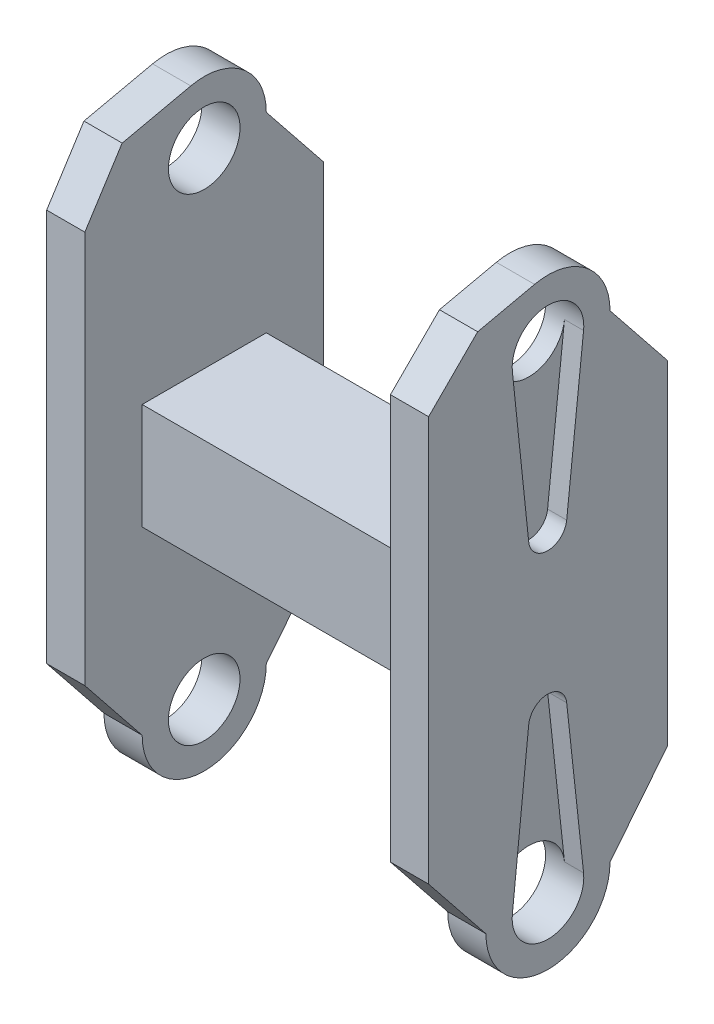
SolidWorks part; units mm, degrees
ref_plane "前视基准面" through (0, 0, 0) normal (0, 0, 1) x (1, 0, 0)
ref_plane "上视基准面" through (0, 0, 0) normal (0, 1, 0) x (1, 0, 0)
ref_plane "右视基准面" through (0, 0, 0) normal (1, 0, 0) x (0, 0, -1)
other "Configuration Table"
sketch "草图1" plane through (0, 0, 0) normal (0, 0, 1) x (1, 0, 0)
  line L0 (0, 35.2024) -> (0, 25) construction
  line L1 (-20, -25) -> (-16, -25)
  line L2 (-20, -25) -> (-20, 25)
  line L3 (-20, 25) -> (-16, 25)
  line L4 (20, -25) -> (20, 25)
  line L5 (-20, -25) -> (-16, -20) construction
  line L6 (-16, -25) -> (-16, -6.113)
  line L7 (-29.4266, 0) -> (27.3187, 0) construction
  line L8 (-16, 25) -> (-16, 5)
  line L9 (-16, 5) -> (16, 5)
  line L10 (16, 5) -> (16, 25)
  line L11 (16, 25) -> (20, 25)
  line L12 (-4, 5) -> (4.8904, -6.113) construction
  line L13 (0, 5) -> (0, -6.113) construction
  line L14 (-16, -6.113) -> (16, -6.113)
  line L15 (16, -6.113) -> (16, -25)
  line L16 (16, -25) -> (20, -25)
  line L17 (-4.8904, -6.113) -> (4, 5) construction
  line L18 (0, -25) -> (0, -39.3339) construction
  line L19 (16, -20) -> (20, -25) construction
  point P0 (0, 0)
  dimension "D1" = 50
  dimension "D2" = 40
  dimension "D3" = 4
  dimension "D4" = 4
  dimension "D5" = 20
  dimension "D6" = 4
  dimension "D7" = 4
extrude "凸台-拉伸1" add sketch "草图1" along normal blind 13
sketch "草图2" plane through (20, 0, 0) normal (1, 0, 0) x (0, 0, -1)
  line L0 (-13, 25) -> (0, 25) construction
  line L1 (0, -25) -> (0, 25) construction
  line L2 (-13, 25) -> (0, 25)
  arc A0 (-13, 25) -> (0, 25) centre (-6.5, 25) cw
extrude "凸台-拉伸2" add sketch "草图2" against normal blind 4
mirror "镜向1" about plane through (0, 0, 0) normal (1, 0, 0) of "凸台-拉伸2"
sketch "草图3" plane through (20, 0, 0) normal (1, 0, 0) x (0, 0, -1)
  line L0 (-10.2295, 24.6087) -> (-8.5176, 8.2913)
  line L1 (-2.7718, 24.5958) -> (-4.5402, 8.2845)
  arc A0 (-2.7718, 24.5958) -> (-10.2295, 24.6087) centre (-6.5, 25) ccw
  arc A1 (-8.5176, 8.2913) -> (-4.5402, 8.2845) centre (-6.5285, 8.5) ccw
  dimension "D1" = 7.5
  dimension "D2" = 4
  dimension "D3" = 16.5
extrude "切除-拉伸1" cut sketch "草图3" against normal blind 2
sketch "草图4" plane through (18, 0, 0) normal (1, 0, 0) x (0, 0, -1)
  circle A0 centre (-6.5, 25) radius 3.75
extrude "切除-拉伸2" cut sketch "草图4" against normal blind 2
sketch "草图6" plane through (-20, 0, 0) normal (-1, 0, 0) x (0, 0, 1)
  circle A0 centre (6.5, 25) radius 3.75
  dimension "D1" = 7.5
extrude "切除-拉伸3" cut sketch "草图6" against normal blind 10
sketch "草图7" plane through (20, 0, 0) normal (1, 0, 0) x (0, 0, -1)
  line L0 (-13, -25) -> (0, -25) construction
  line L1 (0, -25) -> (-13, -25)
  arc A0 (-13, -25) -> (0, -25) centre (-6.5, -25) ccw
extrude "凸台-拉伸3" add sketch "草图7" against normal blind 4
mirror "镜向2" about plane through (0, 0, 0) normal (1, 0, 0) of "凸台-拉伸3"
sketch "草图8" plane through (20, 0, 0) normal (1, 0, 0) x (0, 0, -1)
  line L0 (-8.5176, -8.2913) -> (-10.2295, -24.6087)
  line L1 (-4.5402, -8.2845) -> (-2.7718, -24.5958)
  arc A0 (-10.2295, -24.6087) -> (-2.7718, -24.5958) centre (-6.5, -25) ccw
  arc A1 (-4.5402, -8.2845) -> (-8.5176, -8.2913) centre (-6.5285, -8.5) ccw
  dimension "D1" = 7.5
  dimension "D2" = 4
  dimension "D3" = 16.5
extrude "切除-拉伸4" cut sketch "草图8" against normal blind 2
sketch "草图9" plane through (18, 0, 0) normal (1, 0, 0) x (0, 0, -1)
  circle A0 centre (-6.5, -25) radius 3.75
extrude "切除-拉伸5" cut sketch "草图9" against normal blind 7
sketch "草图11" plane through (-20, 0, 0) normal (-1, 0, 0) x (0, 0, 1)
  circle A0 centre (6.5, -25) radius 3.75
  dimension "D1" = 7.5
extrude "切除-拉伸6" cut sketch "草图11" against normal blind 7
sketch "草图12" plane through (20, 0, 0) normal (1, 0, 0) x (0, 0, -1)
  line L0 (-24.0251, 0) -> (16.6592, 0) construction
  line L1 (0, 25) -> (6, 17.5)
  line L2 (6, 17.5) -> (6, -17.5)
  line L3 (-6.5, 31.5) -> (-6.5, 23.5384) construction
  line L4 (0, 25) -> (0, -25)
  line L5 (0, -25) -> (6, -17.5)
  line L10 (-13, 25) -> (-19, 17.5)
  line L11 (-13, 25) -> (-13, -25)
  line L12 (-19, 17.5) -> (-19, -17.5)
  line L13 (-13, -25) -> (-19, -17.5)
  point P10 (0, 0)
  point P11 (6, 0)
  dimension "D1" = 6
  dimension "D2" = 35
extrude "凸台-拉伸5" add sketch "草图12" against normal blind 4
mirror "镜向8" about plane through (0, 0, 0) normal (1, 0, 0) of "凸台-拉伸5"
sketch "草图13" plane through (20, 0, 0) normal (1, 0, 0) x (0, 0, -1)
  line L0 (-19, 17.5) -> (-19, 28.8916)
  line L1 (-19, 28.8916) -> (-7.9042, 31.3465)
  line L6 (0, -25) -> (6, -17.5)
  line L7 (6, -17.5) -> (6, 17.5)
  line L8 (6, 17.5) -> (0, 25)
  line L9 (-13, 25) -> (-19, 17.5)
  line L10 (-19, 17.5) -> (-19, -17.5)
  line L11 (-19, -17.5) -> (-13, -25)
  line L15 (-13, 25) -> (-19, 17.5)
  arc A2 (-13, -25) -> (0, -25) centre (-6.5, -25) ccw
  arc A3 (0, 25) -> (-13, 25) centre (-6.5, 25) ccw
  arc A5 (-7.9042, 31.3465) -> (-13, 25) centre (-6.5, 25) ccw
  dimension "D1" = 0
extrude "凸台-拉伸6" add sketch "草图13" against normal blind 4
chamfer "倒角1" distance 4 angle 45 1 edges at (18, 28.8916, 19) first distance on face at (18, 5.6958, 19)
mirror "镜向9" about plane through (0, 0, 0) normal (1, 0, 0) of "凸台-拉伸6", "倒角1"
